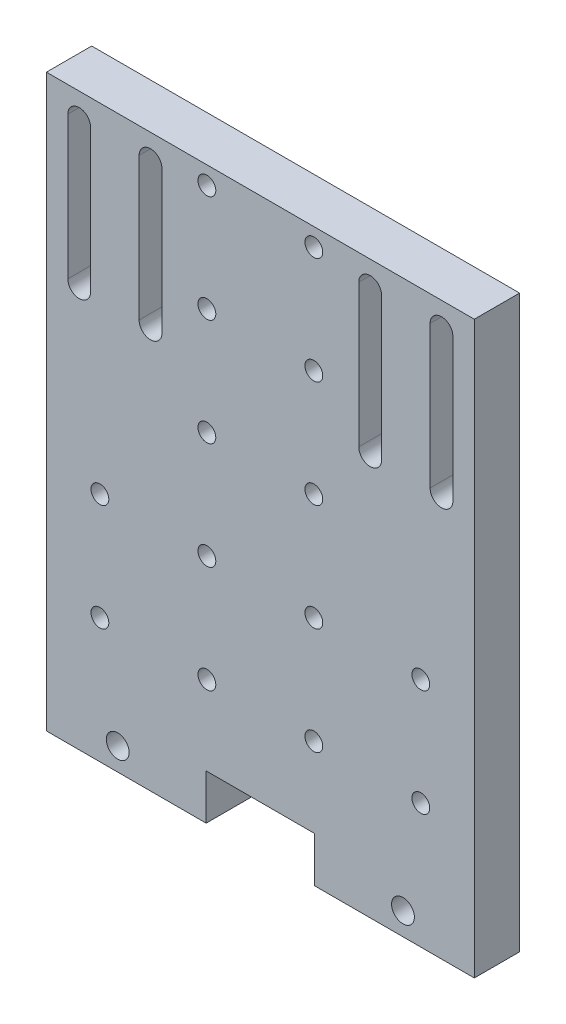
SolidWorks part; units mm, degrees
ref_plane "Front" through (0, 0, 0) normal (0, 0, 1) x (1, 0, 0)
ref_plane "Top" through (0, 0, 0) normal (0, 1, 0) x (1, 0, 0)
ref_plane "Right" through (0, 0, 0) normal (1, 0, 0) x (0, 0, -1)
ref_plane "Plane1" through (0, 0, 118.2886) normal (0, 0, 1) x (1, 0, 0)
sketch "Sketch1" plane through (0, 0, 118.2886) normal (0, 0, 1) x (1, 0, 0)
  line L0 (19.6347, 82.189) -> (19.6347, 2.189)
  line L1 (19.6347, 2.189) -> (42.0347, 2.189)
  line L2 (42.0347, 2.189) -> (42.0347, 8.539)
  line L3 (42.0347, 8.539) -> (57.2347, 8.539)
  line L4 (57.2347, 8.539) -> (57.2347, 2.189)
  line L5 (57.2347, 2.189) -> (79.6347, 2.189)
  line L6 (79.6347, 2.189) -> (79.6347, 82.189)
  line L7 (79.6347, 82.189) -> (19.6347, 82.189)
extrude "Boss-Extrude1" add sketch "Sketch1" against normal blind 6.35
sketch "Sketch2" plane through (0, 0, 111.9386) normal (0, 0, -1) x (-1, 0, 0)
  line L0 (-66.6347, 78.589) -> (-66.6347, 58.589)
  line L1 (-63.4347, 58.589) -> (-63.4347, 78.589)
  arc A0 (-63.4347, 78.589) -> (-66.6347, 78.589) centre (-65.0347, 78.589) ccw
  arc A1 (-66.6347, 58.589) -> (-63.4347, 58.589) centre (-65.0347, 58.589) ccw
extrude "Cut-Extrude1" cut sketch "Sketch2" against normal through all
sketch "Sketch3" plane through (0, 0, 111.9386) normal (0, 0, -1) x (-1, 0, 0)
  line L0 (-35.8347, 78.589) -> (-35.8347, 58.589)
  line L1 (-32.6347, 58.589) -> (-32.6347, 78.589)
  arc A0 (-32.6347, 78.589) -> (-35.8347, 78.589) centre (-34.2347, 78.589) ccw
  arc A1 (-35.8347, 58.589) -> (-32.6347, 58.589) centre (-34.2347, 58.589) ccw
extrude "Cut-Extrude2" cut sketch "Sketch3" against normal through all
sketch "Sketch4" plane through (0, 0, 111.9386) normal (0, 0, -1) x (-1, 0, 0)
  line L0 (-73.4347, 58.589) -> (-73.4347, 78.589)
  line L1 (-76.6347, 78.589) -> (-76.6347, 58.589)
  arc A0 (-76.6347, 58.589) -> (-73.4347, 58.589) centre (-75.0347, 58.589) ccw
  arc A1 (-73.4347, 78.589) -> (-76.6347, 78.589) centre (-75.0347, 78.589) ccw
extrude "Cut-Extrude3" cut sketch "Sketch4" against normal through all
sketch "Sketch5" plane through (0, 0, 111.9386) normal (0, 0, -1) x (-1, 0, 0)
  line L0 (-25.8347, 78.589) -> (-25.8347, 58.589)
  line L1 (-22.6347, 58.589) -> (-22.6347, 78.589)
  arc A0 (-22.6347, 78.589) -> (-25.8347, 78.589) centre (-24.2347, 78.589) ccw
  arc A1 (-25.8347, 58.589) -> (-22.6347, 58.589) centre (-24.2347, 58.589) ccw
extrude "Cut-Extrude4" cut sketch "Sketch5" against normal through all
hole_wizard "Ø2.5 (2.5) Diameter Hole1" positions "Sketch7" profile "Sketch6" hole size "Ø2.5" standard "ANSI Metric"
sketch "Sketch7" plane through (0, 0, 111.9386) normal (0, 0, -1) x (-1, 0, 0)
  point P0 (-27.1347, 19.689)
sketch "Sketch6" plane through (27.1347, 19.689, 111.9386) normal (1, 0, 0) x (0, 1, 0)
  line L0 (0, 0) -> (0, 6.35)
  line L1 (0, 6.35) -> (1.25, 6.35)
  line L2 (1.25, 6.35) -> (1.25, 0)
  line L5 (1.25, 0) -> (0, 0)
  line L11 (0, -6.35) -> (0, 107.95) construction
  dimension "Thru Hole Dia." = 2.5
  dimension "Thru Hole Depth" = 6.35
hole_wizard "Ø3.2 (3.2) Diameter Hole1" positions "Sketch9" profile "Sketch8" hole size "Ø3.2" standard "ANSI Metric"
sketch "Sketch9" plane through (0, 0, 118.2886) normal (0, 0, 1) x (1, 0, 0)
  point P0 (29.6347, 5.364)
sketch "Sketch8" plane through (29.6347, 5.364, 118.2886) normal (1, 0, 0) x (0, -1, 0)
  line L0 (0, 0) -> (0, 6.35)
  line L1 (0, 6.35) -> (1.6, 6.35)
  line L2 (1.6, 6.35) -> (1.6, 0)
  line L5 (1.6, 0) -> (0, 0)
  line L11 (0, -6.35) -> (0, 107.95) construction
  dimension "Thru Hole Dia." = 3.2
  dimension "Thru Hole Depth" = 6.35
hole_wizard "Ø2.5 (2.5) Diameter Hole2" positions "Sketch11" profile "Sketch10" hole size "Ø2.5" standard "ANSI Metric"
sketch "Sketch11" plane through (0, 0, 111.9386) normal (0, 0, -1) x (-1, 0, 0)
  point P0 (-57.1347, 19.689)
sketch "Sketch10" plane through (57.1347, 19.689, 111.9386) normal (1, 0, 0) x (0, 1, 0)
  line L0 (0, 0) -> (0, 6.35)
  line L1 (0, 6.35) -> (1.25, 6.35)
  line L2 (1.25, 6.35) -> (1.25, 0)
  line L5 (1.25, 0) -> (0, 0)
  line L11 (0, -6.35) -> (0, 107.95) construction
  dimension "Thru Hole Dia." = 2.5
  dimension "Thru Hole Depth" = 6.35
hole_wizard "Ø2.5 (2.5) Diameter Hole3" positions "Sketch13" profile "Sketch12" hole size "Ø2.5" standard "ANSI Metric"
sketch "Sketch13" plane through (0, 0, 111.9386) normal (0, 0, -1) x (-1, 0, 0)
  point P0 (-42.1347, 34.689)
sketch "Sketch12" plane through (42.1347, 34.689, 111.9386) normal (1, 0, 0) x (0, 1, 0)
  line L0 (0, 0) -> (0, 6.35)
  line L1 (0, 6.35) -> (1.25, 6.35)
  line L2 (1.25, 6.35) -> (1.25, 0)
  line L5 (1.25, 0) -> (0, 0)
  line L11 (0, -6.35) -> (0, 107.95) construction
  dimension "Thru Hole Dia." = 2.5
  dimension "Thru Hole Depth" = 6.35
hole_wizard "Ø2.5 (2.5) Diameter Hole4" positions "Sketch15" profile "Sketch14" hole size "Ø2.5" standard "ANSI Metric"
sketch "Sketch15" plane through (0, 0, 111.9386) normal (0, 0, -1) x (-1, 0, 0)
  point P0 (-42.1347, 64.689)
sketch "Sketch14" plane through (42.1347, 64.689, 111.9386) normal (1, 0, 0) x (0, 1, 0)
  line L0 (0, 0) -> (0, 6.35)
  line L1 (0, 6.35) -> (1.25, 6.35)
  line L2 (1.25, 6.35) -> (1.25, 0)
  line L5 (1.25, 0) -> (0, 0)
  line L11 (0, -6.35) -> (0, 107.95) construction
  dimension "Thru Hole Dia." = 2.5
  dimension "Thru Hole Depth" = 6.35
hole_wizard "Ø2.5 (2.5) Diameter Hole5" positions "Sketch17" profile "Sketch16" hole size "Ø2.5" standard "ANSI Metric"
sketch "Sketch17" plane through (0, 0, 111.9386) normal (0, 0, -1) x (-1, 0, 0)
  point P0 (-57.1347, 64.689)
sketch "Sketch16" plane through (57.1347, 64.689, 111.9386) normal (1, 0, 0) x (0, 1, 0)
  line L0 (0, 0) -> (0, 6.35)
  line L1 (0, 6.35) -> (1.25, 6.35)
  line L2 (1.25, 6.35) -> (1.25, 0)
  line L5 (1.25, 0) -> (0, 0)
  line L11 (0, -6.35) -> (0, 107.95) construction
  dimension "Thru Hole Dia." = 2.5
  dimension "Thru Hole Depth" = 6.35
hole_wizard "Ø2.5 (2.5) Diameter Hole6" positions "Sketch19" profile "Sketch18" hole size "Ø2.5" standard "ANSI Metric"
sketch "Sketch19" plane through (0, 0, 111.9386) normal (0, 0, -1) x (-1, 0, 0)
  point P0 (-27.1347, 34.689)
sketch "Sketch18" plane through (27.1347, 34.689, 111.9386) normal (1, 0, 0) x (0, 1, 0)
  line L0 (0, 0) -> (0, 6.35)
  line L1 (0, 6.35) -> (1.25, 6.35)
  line L2 (1.25, 6.35) -> (1.25, 0)
  line L5 (1.25, 0) -> (0, 0)
  line L11 (0, -6.35) -> (0, 107.95) construction
  dimension "Thru Hole Dia." = 2.5
  dimension "Thru Hole Depth" = 6.35
hole_wizard "Ø2.5 (2.5) Diameter Hole7" positions "Sketch21" profile "Sketch20" hole size "Ø2.5" standard "ANSI Metric"
sketch "Sketch21" plane through (0, 0, 111.9386) normal (0, 0, -1) x (-1, 0, 0)
  point P0 (-72.1347, 19.689)
sketch "Sketch20" plane through (72.1347, 19.689, 111.9386) normal (1, 0, 0) x (0, 1, 0)
  line L0 (0, 0) -> (0, 6.35)
  line L1 (0, 6.35) -> (1.25, 6.35)
  line L2 (1.25, 6.35) -> (1.25, 0)
  line L5 (1.25, 0) -> (0, 0)
  line L11 (0, -6.35) -> (0, 107.95) construction
  dimension "Thru Hole Dia." = 2.5
  dimension "Thru Hole Depth" = 6.35
hole_wizard "Ø2.5 (2.5) Diameter Hole8" positions "Sketch23" profile "Sketch22" hole size "Ø2.5" standard "ANSI Metric"
sketch "Sketch23" plane through (0, 0, 111.9386) normal (0, 0, -1) x (-1, 0, 0)
  point P0 (-42.1347, 19.689)
sketch "Sketch22" plane through (42.1347, 19.689, 111.9386) normal (1, 0, 0) x (0, 1, 0)
  line L0 (0, 0) -> (0, 6.35)
  line L1 (0, 6.35) -> (1.25, 6.35)
  line L2 (1.25, 6.35) -> (1.25, 0)
  line L5 (1.25, 0) -> (0, 0)
  line L11 (0, -6.35) -> (0, 107.95) construction
  dimension "Thru Hole Dia." = 2.5
  dimension "Thru Hole Depth" = 6.35
hole_wizard "Ø2.5 (2.5) Diameter Hole9" positions "Sketch25" profile "Sketch24" hole size "Ø2.5" standard "ANSI Metric"
sketch "Sketch25" plane through (0, 0, 111.9386) normal (0, 0, -1) x (-1, 0, 0)
  point P0 (-57.1347, 34.689)
sketch "Sketch24" plane through (57.1347, 34.689, 111.9386) normal (1, 0, 0) x (0, 1, 0)
  line L0 (0, 0) -> (0, 6.35)
  line L1 (0, 6.35) -> (1.25, 6.35)
  line L2 (1.25, 6.35) -> (1.25, 0)
  line L5 (1.25, 0) -> (0, 0)
  line L11 (0, -6.35) -> (0, 107.95) construction
  dimension "Thru Hole Dia." = 2.5
  dimension "Thru Hole Depth" = 6.35
hole_wizard "Ø2.5 (2.5) Diameter Hole10" positions "Sketch27" profile "Sketch26" hole size "Ø2.5" standard "ANSI Metric"
sketch "Sketch27" plane through (0, 0, 111.9386) normal (0, 0, -1) x (-1, 0, 0)
  point P0 (-42.1347, 49.689)
sketch "Sketch26" plane through (42.1347, 49.689, 111.9386) normal (1, 0, 0) x (0, 1, 0)
  line L0 (0, 0) -> (0, 6.35)
  line L1 (0, 6.35) -> (1.25, 6.35)
  line L2 (1.25, 6.35) -> (1.25, 0)
  line L5 (1.25, 0) -> (0, 0)
  line L11 (0, -6.35) -> (0, 107.95) construction
  dimension "Thru Hole Dia." = 2.5
  dimension "Thru Hole Depth" = 6.35
hole_wizard "Ø2.5 (2.5) Diameter Hole11" positions "Sketch29" profile "Sketch28" hole size "Ø2.5" standard "ANSI Metric"
sketch "Sketch29" plane through (0, 0, 111.9386) normal (0, 0, -1) x (-1, 0, 0)
  point P0 (-42.1347, 79.689)
sketch "Sketch28" plane through (42.1347, 79.689, 111.9386) normal (1, 0, 0) x (0, 1, 0)
  line L0 (0, 0) -> (0, 6.35)
  line L1 (0, 6.35) -> (1.25, 6.35)
  line L2 (1.25, 6.35) -> (1.25, 0)
  line L5 (1.25, 0) -> (0, 0)
  line L11 (0, -6.35) -> (0, 107.95) construction
  dimension "Thru Hole Dia." = 2.5
  dimension "Thru Hole Depth" = 6.35
hole_wizard "Ø2.5 (2.5) Diameter Hole12" positions "Sketch31" profile "Sketch30" hole size "Ø2.5" standard "ANSI Metric"
sketch "Sketch31" plane through (0, 0, 111.9386) normal (0, 0, -1) x (-1, 0, 0)
  point P0 (-57.1347, 79.689)
sketch "Sketch30" plane through (57.1347, 79.689, 111.9386) normal (1, 0, 0) x (0, 1, 0)
  line L0 (0, 0) -> (0, 6.35)
  line L1 (0, 6.35) -> (1.25, 6.35)
  line L2 (1.25, 6.35) -> (1.25, 0)
  line L5 (1.25, 0) -> (0, 0)
  line L11 (0, -6.35) -> (0, 107.95) construction
  dimension "Thru Hole Dia." = 2.5
  dimension "Thru Hole Depth" = 6.35
hole_wizard "Ø2.5 (2.5) Diameter Hole13" positions "Sketch33" profile "Sketch32" hole size "Ø2.5" standard "ANSI Metric"
sketch "Sketch33" plane through (0, 0, 111.9386) normal (0, 0, -1) x (-1, 0, 0)
  point P0 (-57.1347, 49.689)
sketch "Sketch32" plane through (57.1347, 49.689, 111.9386) normal (1, 0, 0) x (0, 1, 0)
  line L0 (0, 0) -> (0, 6.35)
  line L1 (0, 6.35) -> (1.25, 6.35)
  line L2 (1.25, 6.35) -> (1.25, 0)
  line L5 (1.25, 0) -> (0, 0)
  line L11 (0, -6.35) -> (0, 107.95) construction
  dimension "Thru Hole Dia." = 2.5
  dimension "Thru Hole Depth" = 6.35
hole_wizard "Ø2.5 (2.5) Diameter Hole14" positions "Sketch35" profile "Sketch34" hole size "Ø2.5" standard "ANSI Metric"
sketch "Sketch35" plane through (0, 0, 111.9386) normal (0, 0, -1) x (-1, 0, 0)
  point P0 (-72.1347, 34.689)
sketch "Sketch34" plane through (72.1347, 34.689, 111.9386) normal (1, 0, 0) x (0, 1, 0)
  line L0 (0, 0) -> (0, 6.35)
  line L1 (0, 6.35) -> (1.25, 6.35)
  line L2 (1.25, 6.35) -> (1.25, 0)
  line L5 (1.25, 0) -> (0, 0)
  line L11 (0, -6.35) -> (0, 107.95) construction
  dimension "Thru Hole Dia." = 2.5
  dimension "Thru Hole Depth" = 6.35
hole_wizard "Ø3.2 (3.2) Diameter Hole2" positions "Sketch37" profile "Sketch36" hole size "Ø3.2" standard "ANSI Metric"
sketch "Sketch37" plane through (0, 0, 118.2886) normal (0, 0, 1) x (1, 0, 0)
  point P0 (69.6347, 5.364)
sketch "Sketch36" plane through (69.6347, 5.364, 118.2886) normal (1, 0, 0) x (0, -1, 0)
  line L0 (0, 0) -> (0, 6.35)
  line L1 (0, 6.35) -> (1.6, 6.35)
  line L2 (1.6, 6.35) -> (1.6, 0)
  line L5 (1.6, 0) -> (0, 0)
  line L11 (0, -6.35) -> (0, 107.95) construction
  dimension "Thru Hole Dia." = 3.2
  dimension "Thru Hole Depth" = 6.35
